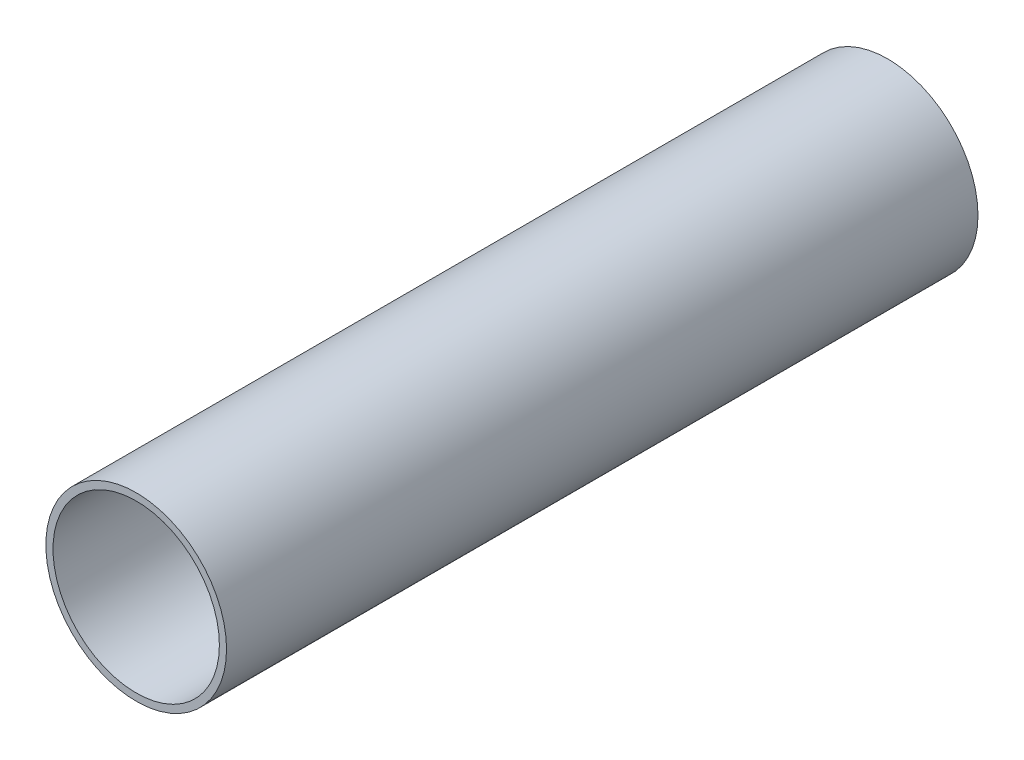
SolidWorks part; units mm, degrees
ref_plane "Front Plane" through (0, 0, 0) normal (0, 0, 1) x (1, 0, 0)
ref_plane "Top Plane" through (0, 0, 0) normal (0, 1, 0) x (1, 0, 0)
ref_plane "Right Plane" through (0, 0, 0) normal (1, 0, 0) x (0, 0, -1)
sketch "Sketch1" plane through (0, 0, 0) normal (0, 0, 1) x (1, 0, 0)
  circle A0 centre (0, 0) radius 25.25
  circle A1 centre (0, 0) radius 23.25
  dimension "D1" = 50.5
  dimension "D2" = 46.5
extrude "Boss-Extrude1" add sketch "Sketch1" along normal blind 210
sketch "Sketch3" plane through (0, 0, 0) normal (0, 1, 0) x (1, 0, 0)
  line L0 (25.25, 0) -> (-25.25, 0) construction
  line L1 (-14, -36) -> (14, -36)
  line L2 (-14, -36) -> (-14, -158)
  line L3 (-14, -158) -> (14, -158)
  line L4 (14, -36) -> (14, -158)
  point P4 (0, -36)
  dimension "D1" = 28
  dimension "D2" = 122
  dimension "D3" = 36
extrude "Cut-Extrude1" cut sketch "Sketch3" against normal up to surface (21.0134 mm away) up to face at (25.25, 0, 210)
ref_axis "Axis1" through (0, 0, 210) along (0, 0, -1)
